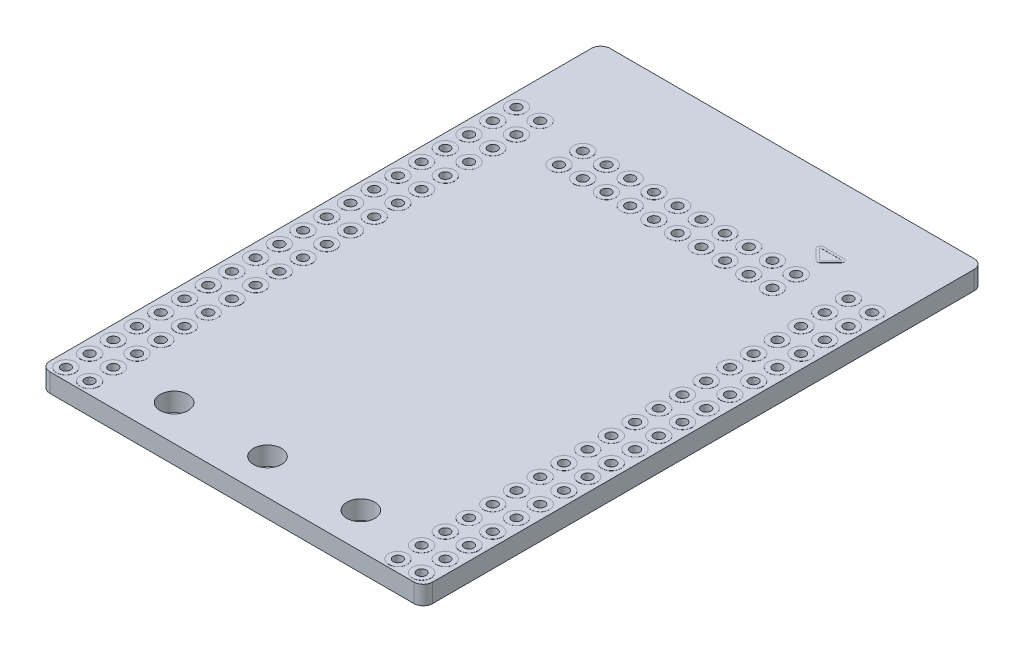
SolidWorks part; units mm, degrees
ref_plane "Front Plane" through (0, 0, 0) normal (0, 0, 1) x (1, 0, 0)
ref_plane "Top Plane" through (0, 0, 0) normal (0, 1, 0) x (1, 0, 0)
ref_plane "Right Plane" through (0, 0, 0) normal (1, 0, 0) x (0, 0, -1)
sketch "Sketch1" plane through (0, 0, 0) normal (0, 1, 0) x (1, 0, 0)
  line L1 (-19.5, -30) -> (19.5, -30)
  line L2 (-20.5, -29) -> (-20.5, 29)
  line L3 (-19.5, 30) -> (19.5, 30)
  line L4 (20.5, -29) -> (20.5, 29)
  line L5 (-20.5, -30) -> (20.5, 30) construction
  line L6 (-20.5, 30) -> (20.5, -30) construction
  arc A0 (-19.5, -30) -> (-20.5, -29) centre (-19.5, -29) cw
  arc A1 (19.5, -30) -> (20.5, -29) centre (19.5, -29) ccw
  arc A2 (19.5, 30) -> (20.5, 29) centre (19.5, 29) cw
  arc A3 (-20.5, 29) -> (-19.5, 30) centre (-19.5, 29) cw
  point P0 (0, 0)
  dimension "D3" = 1
  dimension "D1" = 41
  dimension "D2" = 60
extrude "Boss-Extrude1" add sketch "Sketch1" along normal blind 2
sketch "Sketch4" plane through (0, 2, 0) normal (0, 1, 0) x (1, 0, 0)
  line L0 (-19.5, -30) -> (19.5, -30) construction
  circle A0 centre (0, -26.19) radius 1.5
  circle A1 centre (-10, -26.19) radius 1.5
  circle A2 centre (10, -26.19) radius 1.5
  dimension "D1" = 3
  dimension "D2" = 3.81
  dimension "D3" = 10
  dimension "D4" = 10
extrude "Cut-Extrude2" cut sketch "Sketch4" against normal through all
sketch "Sketch2" plane through (0, 2, 0) normal (0, 1, 0) x (1, 0, 0)
  circle A0 centre (-1.27, 19.01) radius 0.5
  circle A1 centre (-1.27, 19.01) radius 1
  circle A2 centre (0, -26.19) radius 1.5 construction
  dimension "D1" = 1
  dimension "D2" = 0.5
  dimension "D3" = 45.2
  dimension "D4" = 1.27
extrude "Boss-Extrude2" add sketch "Sketch2" along normal blind 0.01
sketch "Sketch3" plane through (0, 2, 0) normal (0, 1, 0) x (1, 0, 0)
  circle A0 centre (-1.27, 19.01) radius 0.5
extrude "Cut-Extrude1" cut sketch "Sketch3" against normal through all both and the other way through all
pattern_linear "LPattern3" count 2 spacing 2.54 along (0, 0, 1) of "Boss-Extrude2", "Cut-Extrude1"
pattern_linear "LPattern4" count 5 spacing 2.54 along (-1, 0, 0) of "LPattern3"
pattern_linear "LPattern5" count 6 spacing 2.54 along (1, 0, 0) of "LPattern3"
sketch "Sketch5" plane through (0, 2, 0) normal (0, 1, 0) x (1, 0, 0)
  line L2 (-20.5, 0) -> (0, 0) construction
  line L3 (-20.5, 29) -> (-20.5, -29) construction
  line L4 (0, 0) -> (0, -30) construction
  line L5 (-19.5, -30) -> (19.5, -30) construction
  circle A0 centre (-19.05, -28.73) radius 0.5
  circle A1 centre (-19.05, -28.73) radius 1
  dimension "D1" = 1
  dimension "D2" = 0.5
  dimension "D3" = 19.05
  dimension "D4" = 28.73
extrude "Boss-Extrude3" add sketch "Sketch5" along normal blind 0.01
sketch "Sketch6" plane through (0, 2, 0) normal (0, 1, 0) x (1, 0, 0)
  circle A0 centre (-19.05, -28.73) radius 0.5
extrude "Cut-Extrude3" cut sketch "Sketch6" against normal through all both and the other way through all
pattern_linear "LPattern6" count 2 spacing 2.54 along (1, 0, 0) of "Boss-Extrude3", "Cut-Extrude3"
pattern_linear "LPattern7" count 20 spacing 2.54 along (0, 0, -1) of "LPattern6"
sketch "Sketch7" plane through (0, 2, 0) normal (0, 1, 0) x (1, 0, 0)
  line L0 (-19.5, -30) -> (19.5, -30) construction
  line L1 (20.5, -29) -> (20.5, 29) construction
  line L2 (0, 0) -> (0, -30) construction
  line L3 (0, 0) -> (20.5, 0) construction
  circle A0 centre (19.05, -28.73) radius 0.5
  circle A1 centre (19.05, -28.73) radius 1
  dimension "D1" = 1
  dimension "D2" = 0.5
  dimension "D3" = 19.05
  dimension "D4" = 28.73
extrude "Boss-Extrude4" add sketch "Sketch7" along normal blind 0.01
sketch "Sketch8" plane through (0, 2, 0) normal (0, 1, 0) x (1, 0, 0)
  circle A0 centre (19.05, -28.73) radius 0.5
extrude "Cut-Extrude4" cut sketch "Sketch8" against normal through all both and the other way through all
pattern_linear "LPattern8" count 2 spacing 2.54 along (-1, 0, 0) of "Boss-Extrude4", "Cut-Extrude4"
pattern_linear "LPattern9" count 20 spacing 2.54 along (0, 0, -1) of "LPattern8"
sketch "Sketch10" plane through (0, 2, 0) normal (0, 1, 0) x (1, 0, 0)
  line L0 (11.4654, 21.5454) -> (12.5946, 22.6746)
  line L1 (12.5593, 22.76) -> (10.3007, 22.76)
  line L2 (10.2654, 22.6746) -> (11.3946, 21.5454)
  line L3 (11.43, 19.01) -> (11.43, 21.51) construction
  line L4 (11.6421, 21.3686) -> (12.7714, 22.4979)
  line L5 (12.5593, 23.01) -> (10.3007, 23.01)
  line L6 (10.0886, 22.4979) -> (11.2179, 21.3686)
  arc A0 (11.4654, 21.5454) -> (11.3946, 21.5454) centre (11.43, 21.5807) cw
  arc A1 (12.5946, 22.6746) -> (12.5593, 22.76) centre (12.5593, 22.71) ccw
  arc A2 (10.3007, 22.76) -> (10.2654, 22.6746) centre (10.3007, 22.71) ccw
  arc A3 (12.7714, 22.4979) -> (12.5593, 23.01) centre (12.5593, 22.71) ccw
  arc A4 (10.3007, 23.01) -> (10.0886, 22.4979) centre (10.3007, 22.71) ccw
  arc A5 (11.6421, 21.3686) -> (11.2179, 21.3686) centre (11.43, 21.5807) cw
  point P10 (12.68, 22.76)
  point P13 (10.18, 22.76)
  dimension "D4" = 0.05
  dimension "D1" = 45
  dimension "D2" = 2.5
  dimension "D3" = 2.5
  dimension "D5" = 0.25
extrude "Boss-Extrude5" add sketch "Sketch10" along normal blind 0.01
